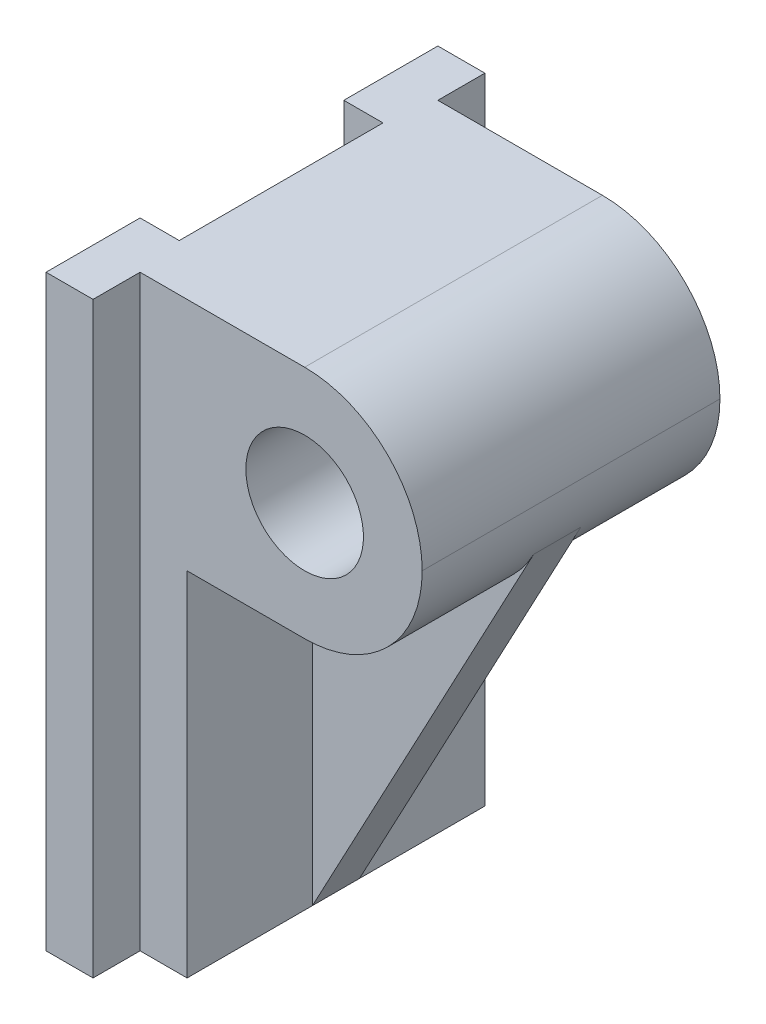
SolidWorks part; units mm, degrees
ref_plane "Front Plane" through (0, 0, 0) normal (0, 0, 1) x (1, 0, 0)
ref_plane "Top Plane" through (0, 0, 0) normal (0, 1, 0) x (1, 0, 0)
ref_plane "Right Plane" through (0, 0, 0) normal (1, 0, 0) x (0, 0, -1)
sketch "Sketch1" plane through (0, 0, 0) normal (0, 1, 0) x (1, 0, 0)
  line L0 (0, 50) -> (0, 26)
  line L1 (0, 26) -> (10, 26)
  line L2 (10, 26) -> (10, -26)
  line L3 (10, -26) -> (0, -26)
  line L4 (0, -26) -> (0, -50)
  line L5 (0, -50) -> (12, -50)
  line L6 (12, -50) -> (12, -38)
  line L7 (12, -38) -> (24, -38)
  line L8 (24, -38) -> (24, 38)
  line L9 (24, 38) -> (12, 38)
  line L10 (12, 38) -> (12, 50)
  line L11 (12, 50) -> (0, 50)
  line L12 (0, 0) -> (68.2353, 0) construction
  dimension "D1" = 12
  dimension "D2" = 12
  dimension "D3" = 10
  dimension "D4" = 52
  dimension "D5" = 100
  dimension "D6" = 12
extrude "Boss-Extrude1" add sketch "Sketch1" along normal blind 150
sketch "Sketch2" plane through (0, 0, -38) normal (0, 0, -1) x (-1, 0, 0)
  line L0 (-84, 120) -> (-24, 120) construction
  line L1 (-24, 150) -> (-84, 150)
  line L2 (-24, 150) -> (-24, 90)
  line L3 (-24, 90) -> (-84, 90)
  line L4 (-84, 150) -> (-84, 90)
  circle A0 centre (-54, 120) radius 15
  dimension "D3" = 30
  dimension "D1" = 60
  dimension "D2" = 60
extrude "Boss-Extrude2" add sketch "Sketch2" against normal blind 76
fillet "Fillet1" radius 30 2 edges at (84, 150, 0) (84, 90, 0)
sketch "Sketch5" plane through (0, 0, 0) normal (0, 0, 1) x (1, 0, 0)
  line L0 (24, 0) -> (80.4706, 105.8824)
  arc A0 (54, 90) -> (84, 120) centre (54, 120) ccw construction
rib "Rib4" sketch "Sketch5" sketch "Sketch5" thickness 12 extrusion direction parallel to sketch draft on no parameters "D1"=12
